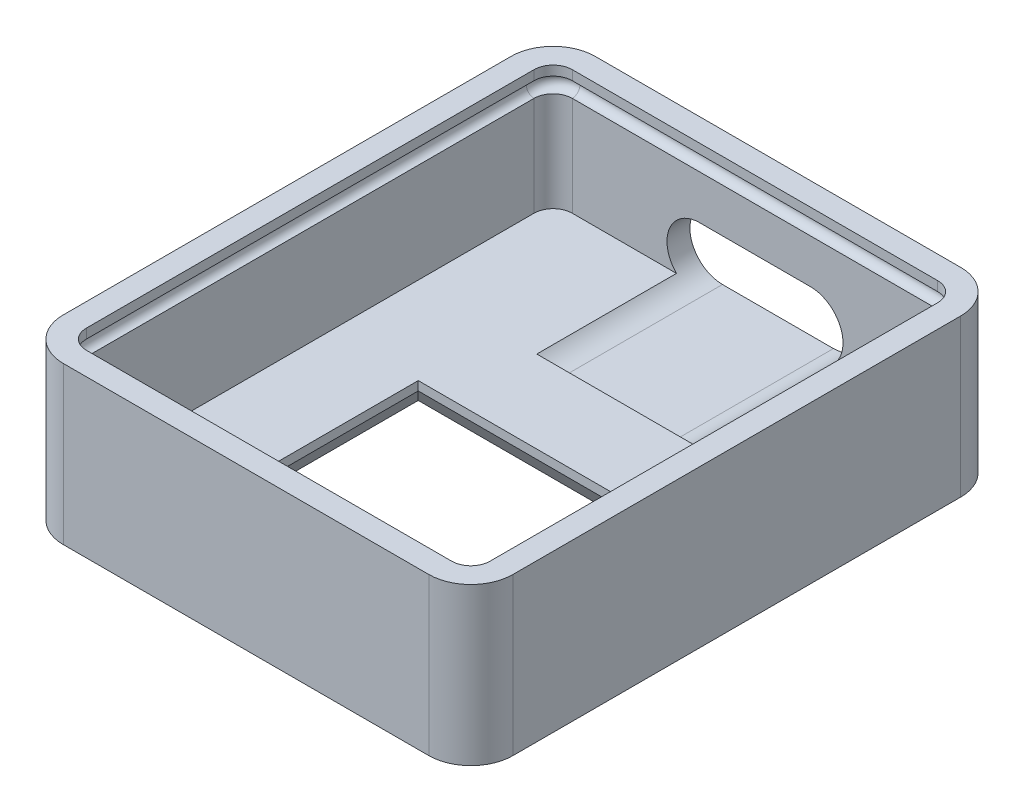
SolidWorks part; units mm, degrees
ref_plane "Front Plane" through (0, 0, 0) normal (0, 0, 1) x (1, 0, 0)
ref_plane "Top Plane" through (0, 0, 0) normal (0, 1, 0) x (1, 0, 0)
ref_plane "Right Plane" through (0, 0, 0) normal (1, 0, 0) x (0, 0, -1)
sketch "Sketch1" plane through (0, 0, 0) normal (0, 1, 0) x (1, 0, 0)
  line L0 (0.8, 25.2) -> (19.9, 25.2)
  line L1 (0, 0) -> (20.7, 0) construction
  line L2 (0, 0) -> (0, 25) construction
  line L3 (0, 25) -> (20.7, 25) construction
  line L4 (20.7, 0) -> (20.7, 25) construction
  line L5 (20.9, 0.8) -> (20.9, 24.2)
  line L6 (0.8, -0.2) -> (19.9, -0.2)
  line L7 (-0.2, 0.8) -> (-0.2, 24.2)
  line L8 (-0.2, -0.2) -> (20.9, -0.2) construction
  line L9 (20.9, -0.2) -> (20.9, 25.2) construction
  line L10 (-0.2, -0.2) -> (-0.2, 25.2) construction
  line L11 (-0.2, 25.2) -> (20.9, 25.2) construction
  line L12 (0.8, 26.4) -> (19.9, 26.4)
  line L13 (22.1, 0.8) -> (22.1, 24.2)
  line L14 (0.8, -1.4) -> (19.9, -1.4)
  line L15 (-1.4, 0.8) -> (-1.4, 24.2)
  arc A0 (19.9, -0.2) -> (20.9, 0.8) centre (19.9, 0.8) ccw
  arc A1 (0.8, -0.2) -> (-0.2, 0.8) centre (0.8, 0.8) cw
  arc A2 (-0.2, 24.2) -> (0.8, 25.2) centre (0.8, 24.2) cw
  arc A3 (20.9, 24.2) -> (19.9, 25.2) centre (19.9, 24.2) ccw
  arc A4 (22.1, 24.2) -> (19.9, 26.4) centre (19.9, 24.2) ccw
  arc A5 (19.9, -1.4) -> (22.1, 0.8) centre (19.9, 0.8) ccw
  arc A6 (0.8, -1.4) -> (-1.4, 0.8) centre (0.8, 0.8) cw
  arc A7 (-1.4, 24.2) -> (0.8, 26.4) centre (0.8, 24.2) cw
  dimension "D4" = 1
  dimension "D5" = 1.2
  dimension "D1" = 20.7
  dimension "D2" = 25
  dimension "D3" = 0.2
extrude "Boss-Extrude7" add sketch "Sketch1" along normal blind 6.5
sketch "Sketch4" plane through (0, 0, 0) normal (0, -1, 0) x (1, 0, 0)
  line L4 (0.8, -26.4) -> (19.9, -26.4)
  line L5 (22.1, -24.2) -> (22.1, -0.8)
  line L6 (19.9, 1.4) -> (0.8, 1.4)
  line L7 (-1.4, -0.8) -> (-1.4, -24.2)
  line L8 (0.8, -26.4) -> (19.9, -26.4)
  line L9 (22.1, -24.2) -> (22.1, -0.8)
  line L10 (19.9, 1.4) -> (0.8, 1.4)
  line L11 (-1.4, -0.8) -> (-1.4, -24.2)
  arc A4 (-1.4, -24.2) -> (0.8, -26.4) centre (0.8, -24.2) ccw
  arc A5 (19.9, -26.4) -> (22.1, -24.2) centre (19.9, -24.2) ccw
  arc A6 (22.1, -0.8) -> (19.9, 1.4) centre (19.9, -0.8) ccw
  arc A7 (0.8, 1.4) -> (-1.4, -0.8) centre (0.8, -0.8) ccw
  arc A8 (-1.4, -24.2) -> (0.8, -26.4) centre (0.8, -24.2) ccw
  arc A9 (19.9, -26.4) -> (22.1, -24.2) centre (19.9, -24.2) ccw
  arc A10 (22.1, -0.8) -> (19.9, 1.4) centre (19.9, -0.8) ccw
  arc A11 (0.8, 1.4) -> (-1.4, -0.8) centre (0.8, -0.8) ccw
  dimension "D1" = 0
extrude "Boss-Extrude8" add sketch "Sketch4" along normal blind 1.7
sketch "Sketch5" plane through (0, 0, -26.4) normal (0, 0, -1) x (-1, 0, 0)
  line L0 (-13.25, 1.2) -> (-7.45, 1.2) construction
  line L1 (-13.25, 2.9) -> (-7.45, 2.9)
  line L2 (-13.25, -0.5) -> (-7.45, -0.5)
  line L3 (-19.9, 6.5) -> (-0.8, 6.5) construction
  line L4 (-0.8, -1.7) -> (-19.9, -1.7) construction
  arc A0 (-13.25, 2.9) -> (-13.25, -0.5) centre (-13.25, 1.2) ccw
  arc A1 (-7.45, -0.5) -> (-7.45, 2.9) centre (-7.45, 1.2) ccw
  point P2 (-10.35, 1.2)
  point P7 (-14.95, 1.2)
  point P8 (-5.75, 1.2)
  point P13 (-10.35, 6.5)
  dimension "D1" = 9.2
  dimension "D2" = 3.4
  dimension "D3" = 1.2
extrude "Cut-Extrude1" cut sketch "Sketch5" against normal blind 8.5 contours L1 A1 L2 A0
sketch "Sketch6" plane through (0, 0, 0) normal (0, 1, 0) x (1, 0, 0)
  line L0 (19.9, 25.2) -> (0.8, 25.2) construction
  line L1 (4.35, 13.6) -> (16.35, 13.6)
  line L2 (4.35, 13.6) -> (4.35, 6.1)
  line L3 (4.35, 6.1) -> (16.35, 6.1)
  line L4 (16.35, 13.6) -> (16.35, 6.1)
  point P4 (10.35, 25.2)
  point P5 (10.35, 13.6)
  dimension "D1" = 12
  dimension "D2" = 7.5
  dimension "D3" = 11.6
extrude "Cut-Extrude2" cut sketch "Sketch6" against normal blind 8.5
chamfer "Chamfer1" distance 0.8 angle 57 4 edges at (10.35, -1.7, -6.1) (4.35, -1.7, -9.85) (10.35, -1.7, -13.6) (16.35, -1.7, -9.85) first distance on face at (10.35, -1.7, -9.85)
ref_plane "Plane1" through (0, 0, -16.4) normal (0, 0, -1) x (-1, 0, 0)
sketch "Sketch9" plane through (0, 6.5, 0) normal (0, 1, 0) x (1, 0, 0)
  line L0 (-1.4, 24.2) -> (-1.4, 0.8) construction
  line L1 (0.8, -1.4) -> (19.9, -1.4) construction
  line L2 (22.1, 0.8) -> (22.1, 24.2) construction
  line L3 (19.9, 26.4) -> (0.8, 26.4) construction
  line L4 (-1.4, 24.2) -> (-1.4, 0.8)
  line L5 (0.8, -1.4) -> (19.9, -1.4)
  line L6 (22.1, 0.8) -> (22.1, 24.2)
  line L7 (19.9, 26.4) -> (0.8, 26.4)
  arc A0 (-1.4, 0.8) -> (0.8, -1.4) centre (0.8, 0.8) ccw construction
  arc A1 (19.9, -1.4) -> (22.1, 0.8) centre (19.9, 0.8) ccw construction
  arc A2 (22.1, 24.2) -> (19.9, 26.4) centre (19.9, 24.2) ccw construction
  arc A3 (0.8, 26.4) -> (-1.4, 24.2) centre (0.8, 24.2) ccw construction
  arc A4 (-1.4, 0.8) -> (0.8, -1.4) centre (0.8, 0.8) ccw
  arc A5 (19.9, -1.4) -> (22.1, 0.8) centre (19.9, 0.8) ccw
  arc A6 (22.1, 24.2) -> (19.9, 26.4) centre (19.9, 24.2) ccw
  arc A7 (0.8, 26.4) -> (-1.4, 24.2) centre (0.8, 24.2) ccw
sketch "Sketch7" plane through (0, 0, -16.4) normal (0, 0, -1) x (-1, 0, 0)
  line L0 (-20.9, 6.5) -> (-20.9, 0) construction
  line L1 (-19.9, 6.5) -> (-22.1, 6.5) construction
  circle A0 centre (-20.9, 5.6) radius 0.4
  dimension "D1" = 0.9
sweep "Cut-Sweep1" cut profiles "Sketch7" path "Sketch9"
sketch "Sketch10" plane through (0, 0, 0) normal (0, 1, 0) x (1, 0, 0)
  line L0 (20.9, 0.8) -> (20.9, 24.2) construction
  line L1 (0.8, -0.2) -> (19.9, -0.2) construction
  line L2 (15.9057, 4) -> (13.4057, 4)
  line L3 (0.8, -0.2) -> (19.9, -0.2) construction
  line L4 (13.4057, 4) -> (13.4057, 3.6)
  line L5 (13.4057, 3.6) -> (15.9057, 3.6)
  line L7 (13.4057, 0) -> (15.9057, 0)
  line L9 (15.4, 0) -> (15.4, -0.2)
  line L10 (15.9057, -0.4) -> (13.4057, -0.4)
  line L11 (13.4057, -0.4) -> (13.4057, 0)
  arc A0 (15.9057, -0.4) -> (15.9057, 4) centre (15.9057, 1.8) ccw
  arc A1 (15.9057, 0) -> (15.9057, 3.6) centre (15.9057, 1.8) ccw
  point P0 (17.9, 1.8)
  point P6 (15.9, 1.8)
  point P10 (17.9, 0)
  dimension "D3" = 0.4
  dimension "D4" = 0.2
  dimension "D1" = 3
  dimension "D2" = 2
  dimension "D5" = 2.5
  dimension "D6" = 2
extrude "Cut-Extrude3" cut sketch "Sketch10" against normal through all and the other way blind 2 contours L11 L10 A0 L2 L4 L5 A1 L7
chamfer "Chamfer2" distance 0.5 angle 45 2 edges at (16.3747, 2, 0.3494) (14.6557, 2, 0.4)
sketch "Sketch11" plane through (0, 0, -3.6) normal (0, 0, -1) x (-1, 0, 0)
  line L0 (-13.4057, 0) -> (-13.4057, -1.1)
  line L1 (-13.4057, -1.1) -> (-14.5057, 0)
  line L2 (-13.4057, 0) -> (-15.9057, 0) construction
  line L3 (-14.5057, 0) -> (-13.4057, 0)
  dimension "D1" = 45
  dimension "D2" = 0.6
extrude "Cut-Extrude4" cut sketch "Sketch11" against normal up to next
sketch "Sketch12" plane through (0, 0, 0) normal (0, 1, 0) x (1, 0, 0)
  circle A0 centre (15.9057, 1.8) radius 0.8
extrude "Boss-Extrude9" add sketch "Sketch12" along normal blind 0.5
chamfer "Chamfer3" distance 0.5 angle 45 1 edges at (15.9057, 0, -1)
equation "\"1.30mm-\"=1.3"
